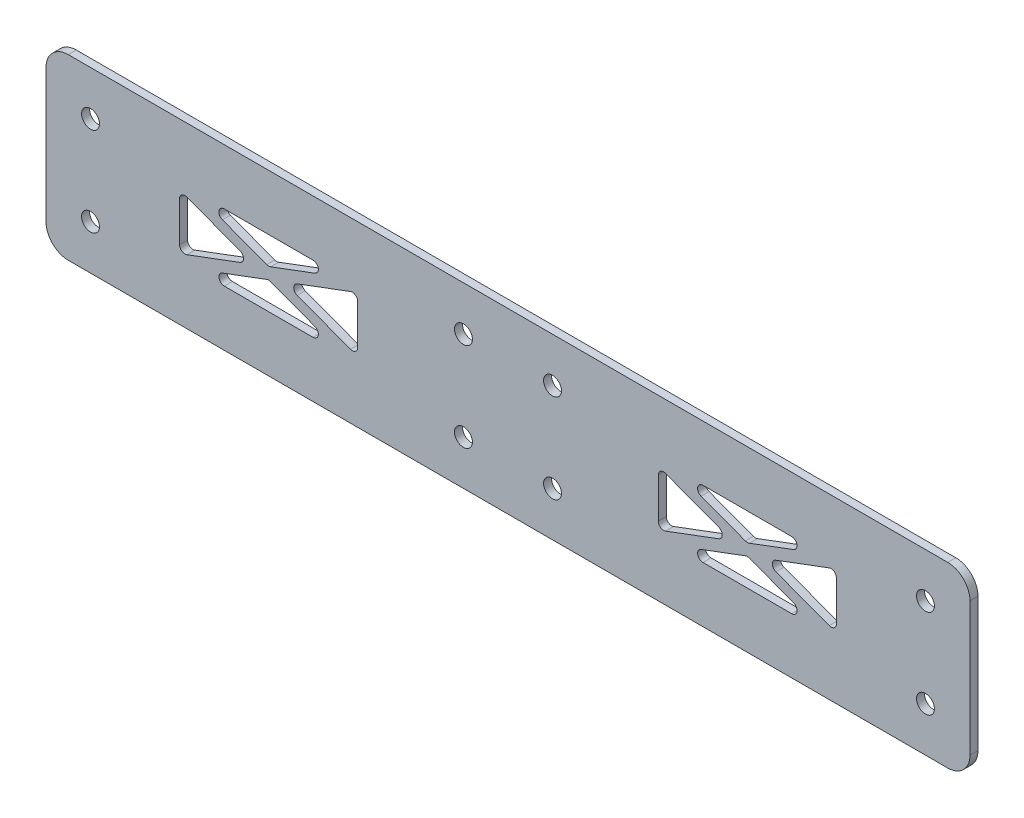
SolidWorks part; units mm, degrees
ref_plane "Front Plane" through (0, 0, 0) normal (0, 0, 1) x (1, 0, 0)
ref_plane "Top Plane" through (0, 0, 0) normal (0, 1, 0) x (1, 0, 0)
ref_plane "Right Plane" through (0, 0, 0) normal (1, 0, 0) x (0, 0, -1)
sketch "Sketch1" plane through (0, 0, 0) normal (0, 0, 1) x (1, 0, 0)
  line L0 (-131.7625, 25.4) -> (-131.7625, -25.4)
  line L1 (-131.7625, -25.4) -> (131.7625, -25.4)
  line L2 (131.7625, -25.4) -> (131.7625, 25.4)
  line L3 (131.7625, 25.4) -> (-131.7625, 25.4)
  line L4 (0, 0) -> (0, -152.4) construction
  line L5 (-25.4, 0) -> (-25.4, -152.4) construction
  line L6 (25.4, 0) -> (25.4, -152.4) construction
  line L7 (-25.4, 0) -> (25.4, 0) construction
  line L8 (-25.4, -152.4) -> (25.4, -152.4) construction
  point P4 (0, -25.4)
  point P5 (-131.7625, 0)
  dimension "D1" = 50.8
  dimension "D2" = 263.525
  dimension "D3" = 152.4
  dimension "D4" = 25.4
  dimension "D5" = 25.4
extrude "Boss-Extrude1" add sketch "Sketch1" along normal mid plane 2.286 contours L5 L7 L6 L1 L2 L3 L0 | L4 L7 L5 L1 | L7 L4 L1 L6 | L1 L4 L8 L6 | L4 L1 L5 L8 region at (0, 0, 0)
hole_wizard "#10 Clearance Hole1" positions "Sketch3" profile "Sketch2" hole size "#10" standard "ANSI Inch" end condition through all
sketch "Sketch3" plane through (0, 0, 1.143) normal (0, 0, 1) x (1, 0, 0)
  line L0 (-131.7625, 25.4) -> (-131.7625, -25.4) construction
  line L1 (131.7625, 25.4) -> (-131.7625, 25.4) construction
  line L2 (-131.7625, -25.4) -> (131.7625, -25.4) construction
  line L4 (-12.7, -12.7) -> (12.7, -12.7) construction
  line L5 (-12.7, -12.7) -> (-12.7, 12.7) construction
  line L6 (-12.7, 12.7) -> (12.7, 12.7) construction
  line L7 (12.7, -12.7) -> (12.7, 12.7) construction
  line L8 (-12.7, -12.7) -> (12.7, 12.7) construction
  line L9 (-12.7, 12.7) -> (12.7, -12.7) construction
  line L11 (0, -60.3453) -> (0, 57.9969) construction
  point P0 (-119.0625, 12.7)
  point P25 (-119.0625, -12.7)
  point P30 (-12.7, 12.7)
  point P32 (-12.7, -12.7)
  point P34 (12.7, -12.7)
  point P36 (12.7, 12.7)
  point P70 (0, 0)
  point P78 (119.0625, 12.7)
  point P79 (119.0625, -12.7)
  dimension "D5" = 25.4
  dimension "D1" = 12.7
  dimension "D2" = 12.7
  dimension "D4" = 12.7
  dimension "D6" = 12.7
  dimension "D7" = 25.4
  dimension "D3" = 2
sketch "Sketch2" plane through (-119.0625, 12.7, 1.143) normal (1, 0, 0) x (0, -1, 0)
  line L0 (0, 0) -> (0, 2.286)
  line L1 (0, 2.286) -> (2.5527, 2.286)
  line L2 (2.5527, 2.286) -> (2.5527, 0)
  line L5 (2.5527, 0) -> (0, 0)
  line L11 (0, -6.35) -> (0, 107.95) construction
  dimension "Thru Hole Dia." = 5.1054
  dimension "Thru Hole Depth" = 2.286
fillet "Fillet1" radius 6.35 4 edges at (131.7625, -25.4, 0) (-131.7625, -25.4, 0) (131.7625, 25.4, 0) (-131.7625, 25.4, 0)
sketch "Sketch4" plane through (0, 0, 1.143) normal (0, 0, 1) x (1, 0, 0)
  line L0 (-131.7625, 19.05) -> (-131.7625, -19.05) construction
  line L1 (-93.6625, 9.525) -> (-42.8625, 9.525)
  line L2 (-93.6625, 9.525) -> (-93.6625, -9.525)
  line L3 (-93.6625, -9.525) -> (-42.8625, -9.525)
  line L4 (-42.8625, 9.525) -> (-42.8625, -9.525)
  line L5 (-93.6625, 9.525) -> (-42.8625, -9.525) construction
  line L6 (-93.6625, -9.525) -> (-42.8625, 9.525) construction
  line L7 (42.8625, 9.525) -> (93.6625, 9.525)
  line L8 (42.8625, 9.525) -> (42.8625, -9.525)
  line L9 (42.8625, -9.525) -> (93.6625, -9.525)
  line L10 (93.6625, 9.525) -> (93.6625, -9.525)
  line L11 (42.8625, 9.525) -> (93.6625, -9.525) construction
  line L12 (42.8625, -9.525) -> (93.6625, 9.525) construction
  line L13 (131.7625, -19.05) -> (131.7625, 19.05) construction
  line L14 (-94.1976, 8.098) -> (-43.3976, -10.952)
  line L15 (-93.1274, -10.952) -> (-42.3274, 8.098)
  line L16 (43.3976, -10.952) -> (94.1976, 8.098)
  line L17 (42.3274, 8.098) -> (93.1274, -10.952)
  line L18 (-93.1274, 10.952) -> (-42.3274, -8.098)
  line L19 (-94.1976, -8.098) -> (-43.3976, 10.952)
  line L20 (42.3274, -8.098) -> (93.1274, 10.952)
  line L21 (43.3976, 10.952) -> (94.1976, -8.098)
  point P0 (-68.2625, 0)
  point P5 (68.2625, 0)
  point P10 (-131.7625, 0)
  dimension "D1" = 38.1
  dimension "D2" = 38.1
  dimension "D3" = 50.8
  dimension "D4" = 19.05
  dimension "D5" = 1.524
  dimension "D6" = 1.524
extrude "Cut-Extrude1" cut sketch "Sketch4" against normal through all contours L2 L19 L14 | L18 L19 L1 | L15 L18 L4 | L15 L3 L14 | L17 L16 L9 | L8 L20 L17 | L7 L21 L20 | L16 L21 L10 region at (-68.2625, 6.8925, 1.143) region at (-86.6426, 0, 1.143) region at (-49.8824, 0, 1.143) region at (-68.2625, -6.8925, 1.143) region at (68.2625, 6.8925, 1.143) region at (49.8824, 0, 1.143) region at (86.6426, 0, 1.143) region at (68.2625, -6.8925, 1.143)
fillet "Fillet2" radius 1.524 24 edges at (93.6625, 7.8974, 0) (93.6625, -7.8974, 0) (72.6029, 0, 0) (89.3221, -9.525, 0) (47.2029, -9.525, 0) (68.2625, -1.6276, 0) (-42.8625, 7.8974, 0) (-42.8625, -7.8974, 0) (-63.9221, 0, 0) (-47.2029, 9.525, 0) (-68.2625, 1.6276, 0) (-89.3221, 9.525, 0) (-72.6029, 0, 0) (-93.6625, 7.8974, 0) (-68.2625, -1.6276, 0) (-47.2029, -9.525, 0) (-89.3221, -9.525, 0) (63.9221, 0, 0) (42.8625, -7.8974, 0) (42.8625, 7.8974, 0) (89.3221, 9.525, 0) (68.2625, 1.6276, 0) (47.2029, 9.525, 0) (-93.6625, -7.8974, 0)
